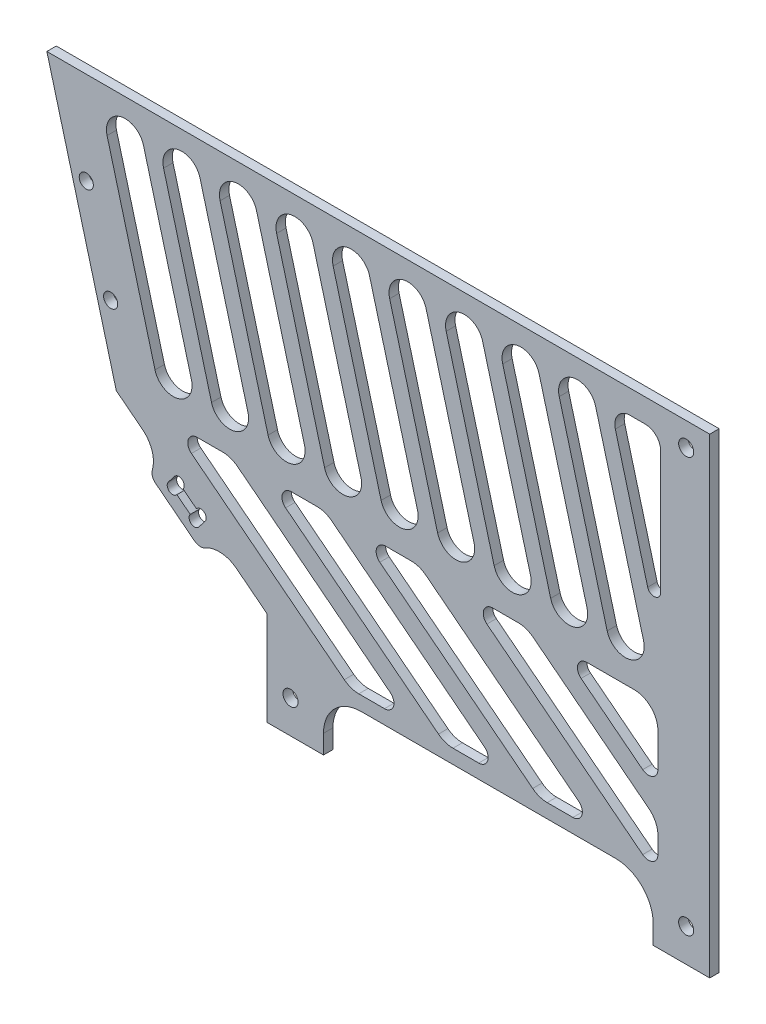
SolidWorks part; units mm, degrees
material "环氧树脂FR-4"
ref_plane "前视基准面" through (0, 0, 0) normal (0, 0, 1) x (1, 0, 0)
ref_plane "上视基准面" through (0, 0, 0) normal (0, 1, 0) x (1, 0, 0)
ref_plane "右视基准面" through (0, 0, 0) normal (1, 0, 0) x (0, 0, -1)
sketch "草图1" plane through (0, 0, 0) normal (0, 0, 1) x (1, 0, 0)
  line L1 (46.7357, -100) -> (140.7357, -100)
  line L5 (140.7357, 0) -> (0, 0)
  line L7 (46.7357, -80) -> (46.7357, -100)
  line L8 (46.7357, -80) -> (14.7372, -55)
  line L9 (14.7372, -55) -> (0, 0)
  line L10 (140.7357, 0) -> (140.7357, -100)
  circle A0 centre (187.9731, -24) radius 55 construction
  point P6 (187.9731, -24)
  dimension "D9" = 110
  dimension "D2" = 94
  dimension "D3" = 75
  dimension "D4" = 100
  dimension "D5" = 55
  dimension "D7" = 76
  dimension "D10" = 20
  dimension "D11" = 38
extrude "凸台-拉伸1" add sketch "草图1" along normal blind 2
sketch "草图2" plane through (0, 0, 0) normal (0, 0, -1) x (-1, 0, 0)
  line L0 (-46.7357, -100) -> (-140.7357, -100) construction
  line L2 (-135.7357, -93) -> (-51.7357, -93) construction
  line L3 (-140.7357, -100) -> (-140.7357, 0) construction
  circle A0 centre (-135.7357, -93) radius 1.6
  circle A1 centre (-51.7357, -93) radius 1.6
  dimension "D2" = 3.2
  dimension "D1" = 7
  dimension "D3" = 5
  dimension "D4" = 84
extrude "切除-拉伸1" cut sketch "草图2" against normal blind 60
sketch "草图5" plane through (0, 0, 2) normal (0, 0, 1) x (1, 0, 0)
  line L0 (0, 0) -> (14.7372, -55) construction
  line L1 (30.6927, -45) -> (22.9653, -47.0706)
  line L2 (30.6927, -45) -> (20.5106, -7)
  line L3 (20.5106, -7) -> (12.7832, -9.0706)
  line L4 (22.9653, -47.0706) -> (12.7832, -9.0706)
  line L5 (140.7357, 0) -> (0, 0) construction
  circle A0 centre (16.6469, -8.0353) radius 4
  circle A1 centre (26.829, -46.0353) radius 4
  dimension "D1" = 8
  dimension "D2" = 38
  dimension "D3" = 10
  dimension "D4" = 7
extrude "切除-拉伸3" cut sketch "草图5" against normal through all contours A1 L2 A0 L4 | L3 A0 | L3 A0 | L1 A1 | L1 A1 region at (27.2684, -47.6751, 2) region at (21.7379, -27.0353, 2) region at (26.3896, -44.3955, 2) region at (17.0863, -9.6751, 2) region at (16.2075, -6.3955, 2)
pattern_linear "阵列(线性)1" count 9 spacing 12 along (1, 0, 0) of "切除-拉伸3"
sketch "草图6" plane through (0, 0, 2) normal (0, 0, 1) x (1, 0, 0)
  line L0 (119.5982, -5) -> (130.3162, -45)
  line L2 (130.3162, -45) -> (130.3162, -5)
  line L3 (130.3162, -5) -> (119.5982, -5)
  line L4 (140.7357, 0) -> (0, 0) construction
  line L5 (102.6927, -45) -> (92.5106, -7) construction
  line L7 (126.6927, -45) -> (116.5106, -7) construction
  dimension "D1" = 3.5
  dimension "D2" = 40
  dimension "D3" = 5
extrude "切除-拉伸4" cut sketch "草图6" against normal through all
fillet "圆角1" radius 3.25 2 edges at (130.3162, -5, 1) (119.5982, -5, 1)
fillet "圆角2" radius 1.4 1 edges at (130.3162, -45, 1)
sketch "草图8" plane through (0, 0, 2) normal (0, 0, 1) x (1, 0, 0)
  line L0 (8.371, -19.65) -> (13.5474, -38.9685) construction
  line L1 (0, 0) -> (14.7372, -55) construction
  line L2 (140.7357, 0) -> (0, 0) construction
  circle A0 centre (8.371, -19.65) radius 1.5
  circle A1 centre (13.5474, -38.9685) radius 1.5
  dimension "D2" = 3
  dimension "D1" = 3
  dimension "D3" = 19.65
  dimension "D4" = 20
extrude "切除-拉伸6" cut sketch "草图8" against normal through all
sketch "草图9" [suppressed] plane through (0, 0, 0) normal (0, 0, 1) x (1, 0, 0)
  line L0 (13.3975, -50) -> (14.7372, -55)
  line L5 (45.396, -75) -> (13.3975, -50)
  line L6 (0, 0) -> (13.3975, -50) construction
  line L7 (14.7372, -55) -> (40.336, -75)
  line L8 (40.336, -75) -> (45.396, -75)
  dimension "D1" = 5
extrude "凸台-拉伸3" [suppressed] add sketch "草图9" along normal up to surface (2 mm away)
sketch "草图10" [suppressed] plane through (0, 0, 2) normal (0, 0, 1) x (1, 0, 0)
  line L0 (31.3237, -61.3058) -> (30, -63)
  line L1 (30, -63) -> (38.1165, -69.3413)
  line L2 (38.1165, -69.3413) -> (39.4402, -67.6471)
  line L3 (39.4402, -67.6471) -> (31.3237, -61.3058)
  line L4 (139.396, 0) -> (0, 0) construction
  dimension "D1" = 38
  dimension "D2" = 63
  dimension "D3" = 30
  dimension "D4" = 10.3
  dimension "D5" = 2.15
extrude "切除-拉伸7" [suppressed] cut sketch "草图10" against normal up to next
sketch "草图11" [suppressed] plane through (0, 0, 2) normal (0, 0, 1) x (1, 0, 0)
  line L0 (35.3819, -64.4764) -> (34.0583, -66.1707) construction
  line L1 (39.4402, -67.6471) -> (31.3237, -61.3058) construction
  line L2 (30, -63) -> (38.1165, -69.3413) construction
  line L3 (30.6618, -62.1529) -> (38.7783, -68.4942) construction
  line L4 (31.3237, -61.3058) -> (30, -63) construction
  line L5 (38.1165, -69.3413) -> (39.4402, -67.6471) construction
  line L6 (30, -63) -> (31.3237, -61.3058) construction
  circle A2 centre (32.2299, -62.0138) radius 1.15
  circle A3 centre (30.9062, -63.708) radius 1.15
  circle A4 centre (37.2103, -68.6333) radius 1.15
  circle A5 centre (38.534, -66.9391) radius 1.15
  dimension "D1" = 2.3
extrude "切除-拉伸8" [suppressed] cut sketch "草图11" against normal through all contours A3 A2 | A2 A3 | A5 A4 | A4 A5
sketch "草图12" plane through (0, 0, 2) normal (0, 0, 1) x (1, 0, 0)
  line L0 (140.7357, 0) -> (0, 0) construction
  line L1 (140.7357, -100) -> (140.7357, 0) construction
  circle A0 centre (135.7357, -5) radius 1.6
  dimension "D3" = 3.2
  dimension "D1" = 5
  dimension "D2" = 5
extrude "切除-拉伸9" cut sketch "草图12" against normal through all
sketch "草图15" plane through (0, 0, 2) normal (0, 0, 1) x (1, 0, 0)
  line L0 (46.7357, -100) -> (140.7357, -100) construction
  line L1 (128.7357, -112) -> (58.7357, -112)
  line L2 (128.7357, -112) -> (128.7357, -88)
  line L3 (128.7357, -88) -> (58.7357, -88)
  line L4 (58.7357, -112) -> (58.7357, -88)
  line L5 (128.7357, -112) -> (58.7357, -88) construction
  line L6 (128.7357, -88) -> (58.7357, -112) construction
  point P0 (93.7357, -100)
  dimension "D1" = 24
  dimension "D2" = 70
extrude "切除-拉伸13" cut sketch "草图15" against normal through all
fillet "圆角10" radius 8 2 edges at (128.7357, -88, 1) (58.7357, -88, 1)
sketch "草图13" plane through (0, 0, 2) normal (0, 0, 1) x (1, 0, 0)
  line L5 (26.1071, -55) -> (64.5053, -85)
  line L6 (64.5053, -85) -> (77.4995, -85)
  line L7 (77.4995, -85) -> (39.1012, -55)
  line L8 (39.1012, -55) -> (26.1071, -55)
  line L9 (14.7372, -55) -> (46.7357, -80) construction
  line L10 (140.7357, 0) -> (0, 0) construction
  line L11 (46.7357, -100) -> (58.7357, -100) construction
  dimension "D1" = 7
  dimension "D2" = 8
  dimension "D3" = 55
  dimension "D4" = 15
extrude "切除-拉伸11" cut sketch "草图13" against normal through all
fillet "圆角5" radius 2 2 edges at (77.4995, -85, 1) (26.1071, -55, 1)
fillet "圆角6" radius 5 2 edges at (64.5053, -85, 1) (39.1012, -55, 1)
pattern_linear "阵列(线性)2" count 3 spacing 20 along (1, 0, 0) of "切除-拉伸11", "圆角5", "圆角6"
sketch "草图14" plane through (0, 0, 2) normal (0, 0, 1) x (1, 0, 0)
  line L0 (86.9164, -71.258) -> (84.2609, -74.6569) construction
  line L1 (70.6842, -58.576) -> (103.1487, -83.9401) construction
  line L2 (92.9224, -81.424) -> (60.4579, -56.0599) construction
  line L3 (88.8469, -55) -> (129.7357, -86.9459)
  line L4 (129.7357, -86.9459) -> (129.7357, -76.7938)
  line L5 (129.7357, -76.7938) -> (101.841, -55)
  line L6 (101.841, -55) -> (88.8469, -55)
  line L7 (108.8416, -55) -> (129.7357, -71.3243)
  line L8 (129.7357, -71.3243) -> (129.7357, -55)
  line L9 (129.7357, -55) -> (108.8416, -55)
  line L10 (140.7357, -100) -> (140.7357, 0) construction
  line L11 (112.9224, -81.424) -> (80.4579, -56.0599) construction
  line L12 (77.3796, -55) -> (71.9155, -55) construction
  dimension "D1" = 11
  dimension "D2" = 6
  dimension "D3" = 4.31
  dimension "D4" = 8
extrude "切除-拉伸12" cut sketch "草图14" against normal through all
fillet "圆角8" radius 2 4 edges at (108.8416, -55, 1) (129.7357, -71.3243, 1) (129.7357, -86.9459, 1) (88.8469, -55, 1)
fillet "圆角9" radius 5 3 edges at (129.7357, -55, 1) (129.7357, -76.7938, 1) (101.841, -55, 1)
sketch "草图18" plane through (0, 0, 0) normal (0, 0, -1) x (-1, 0, 0)
  line L0 (-35.6195, -71.315) -> (-32.5412, -75.2551)
  line L1 (-14.7372, -55) -> (-46.7357, -80) construction
  line L2 (-32.5412, -75.2551) -> (-21.903, -66.9437)
  line L3 (-21.903, -66.9437) -> (-24.9813, -63.0036)
  line L4 (-24.9813, -63.0036) -> (-35.6195, -71.315)
  point P5 (-30.3004, -67.1593)
  dimension "D1" = 5
  dimension "D2" = 13.5
  dimension "D3" = 13
extrude "凸台-拉伸6" add sketch "草图18" against normal up to surface (2 mm away) up to face at (123.1722, -60.689, 2)
sketch "草图17" plane through (0, 0, 0) normal (0, 0, 1) x (1, 0, 0)
  line L9 (27.1157, -64.576) -> (33.5774, -69.6244)
  line L11 (33.5774, -69.6244) -> (32.2538, -71.3186)
  line L12 (32.2538, -71.3186) -> (25.7921, -66.2702)
  line L13 (25.7921, -66.2702) -> (27.1157, -64.576)
  line L14 (26.4539, -65.4231) -> (32.9156, -70.4715) construction
  line L15 (14.7372, -55) -> (24.9813, -63.0036) construction
  line L16 (14.7372, -55) -> (24.9813, -63.0036) construction
  line L17 (27.2221, -71.0994) -> (39.7135, -55.1111) construction
  line L18 (32.5412, -75.2551) -> (21.903, -66.9437) construction
  line L19 (30.3466, -67.1002) -> (29.0229, -68.7944) construction
  circle A6 centre (32.6712, -68.9164) radius 1.15
  circle A7 centre (31.3476, -70.6106) radius 1.15
  circle A8 centre (26.6983, -66.9782) radius 1.15
  circle A9 centre (28.022, -65.284) radius 1.15
  dimension "D4" = 2.3
  dimension "D1" = 8.2
  dimension "D2" = 2.15
  dimension "D3" = 1
extrude "切除-拉伸16" cut sketch "草图17" along normal through all contours L9 A9 | L9 A9 A8 | A9 L13 A8 | A9 A8 L12 | L12 A8 | A8 A9 | A9 A8 L12 A7 A6 L9 | A7 A6 L9 | A6 A7 L12 | L9 A6 | L12 A7 | A7 L11 A6 | A6 A7 region at (28.3224, -64.8994, 0) region at (26.6121, -65.5467, 0) region at (27.7364, -65.6496, 0) region at (29.6848, -67.9473, 0) region at (26.9839, -66.6127, 0) region at (26.3978, -67.3628, 0) region at (27.3601, -66.1311, 0) region at (32.9717, -68.5318, 0) region at (32.3856, -69.282, 0) region at (32.7574, -70.3479, 0) region at (32.0094, -69.7635, 0) region at (31.6331, -70.2451, 0) region at (31.0471, -70.9952, 0)
fillet "圆角11" radius 6 2 edges at (24.9813, -63.0036, 1) (35.6195, -71.315, 1)
fillet "圆角12" radius 2 2 edges at (21.903, -66.9437, 1) (32.5412, -75.2551, 1)
